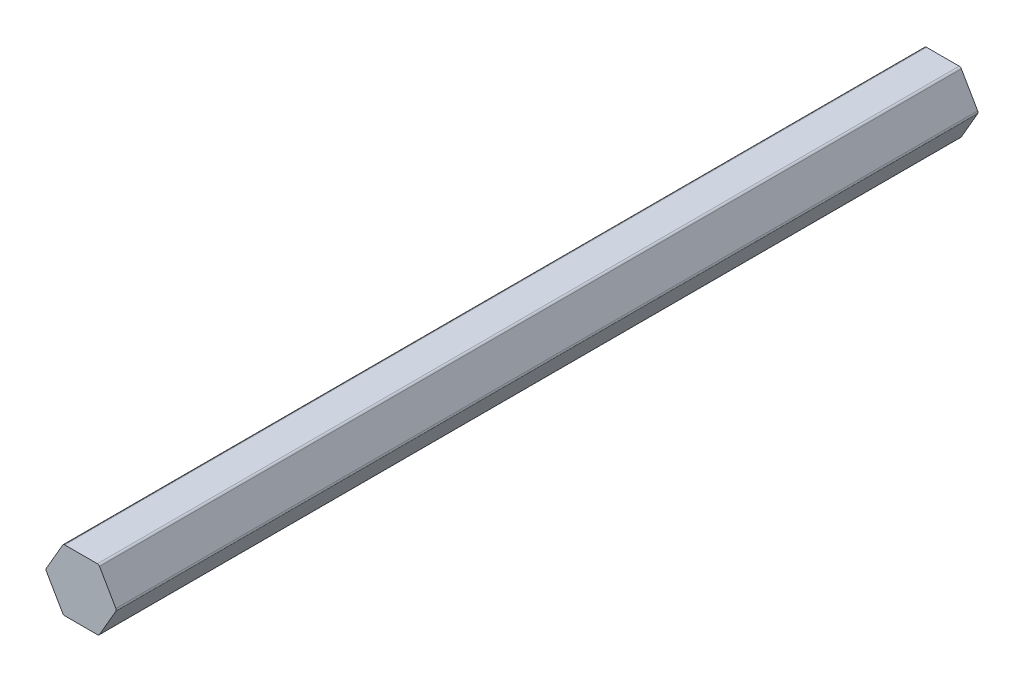
SolidWorks part; units mm, degrees
material "7075-T6 (SN)"
ref_plane "Front Plane" through (0, 0, 0) normal (0, 0, 1) x (1, 0, 0)
ref_plane "Top Plane" through (0, 0, 0) normal (0, 1, 0) x (1, 0, 0)
ref_plane "Right Plane" through (0, 0, 0) normal (1, 0, 0) x (0, 0, -1)
sketch "Sketch1" plane through (0, 0, 0) normal (0, 0, 1) x (1, 0, 0)
  line L0 (3.3655, -5.8293) -> (-3.3655, 5.8293) construction
  line L1 (6.7311, 0) -> (-6.7311, 0) construction
  line L2 (-3.3655, -5.8293) -> (3.3655, 5.8293) construction
  line L3 (-7.171, -0.254) -> (-3.8055, -6.0833)
  line L4 (-3.3655, -6.3373) -> (3.3655, -6.3373)
  line L5 (3.8055, -6.0833) -> (7.171, -0.254)
  line L6 (7.171, 0.254) -> (3.8055, 6.0833)
  line L7 (3.3655, 6.3373) -> (-3.3655, 6.3373)
  line L8 (-3.8055, 6.0833) -> (-7.171, 0.254)
  circle A0 centre (0, 0) radius 6.3373 construction
  arc A1 (-3.8055, -6.0833) -> (-3.3655, -6.3373) centre (-3.3655, -5.8293) ccw
  arc A2 (3.3655, -6.3373) -> (3.8055, -6.0833) centre (3.3655, -5.8293) ccw
  arc A3 (7.171, -0.254) -> (7.171, 0.254) centre (6.7311, 0) ccw
  arc A4 (3.8055, 6.0833) -> (3.3655, 6.3373) centre (3.3655, 5.8293) ccw
  arc A5 (-3.3655, 6.3373) -> (-3.8055, 6.0833) centre (-3.3655, 5.8293) ccw
  arc A6 (-7.171, 0.254) -> (-7.171, -0.254) centre (-6.7311, 0) ccw
  point P18 (0, 0)
  point P19 (0, 0)
  point P21 (0, 0)
  dimension "D1" = 12.6746
  dimension "D2" = 0.508
extrude "Boss-Extrude1" add sketch "Sketch1" along normal mid plane 177.8
ref_axis "Axis1" through (0, 0, -251.46) along (0, 0, 1)
